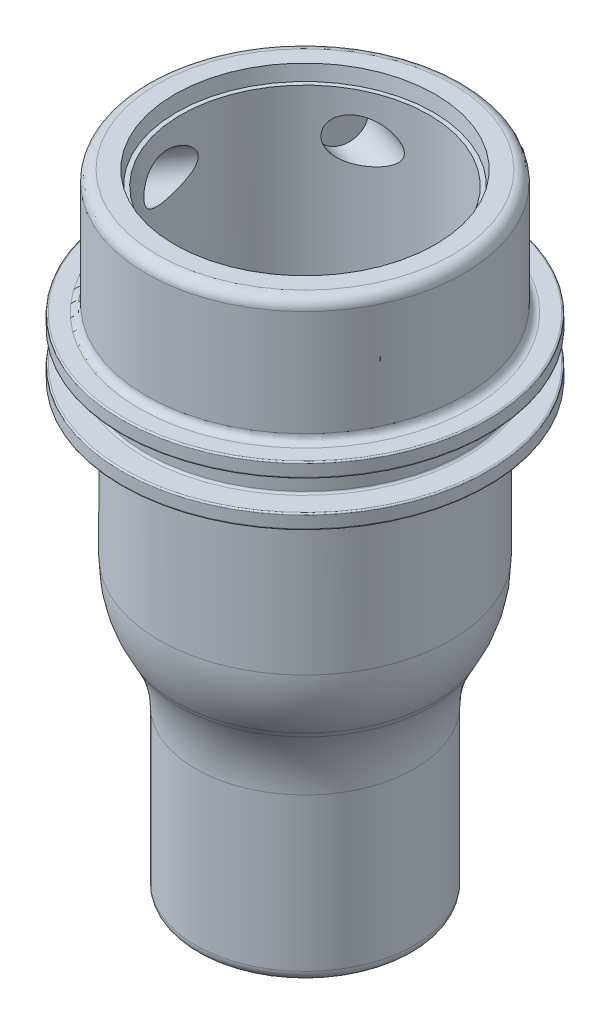
SolidWorks part; units mm, degrees
ref_plane "Front Plane" through (0, 0, 0) normal (0, 0, 1) x (1, 0, 0)
ref_plane "Top Plane" through (0, 0, 0) normal (0, 1, 0) x (1, 0, 0)
ref_plane "Right Plane" through (0, 0, 0) normal (1, 0, 0) x (0, 0, -1)
sketch "Sketch2" plane through (0, 0, 0) normal (0, 0, 1) x (1, 0, 0)
  line L0 (7.62, 0) -> (7.62, 17.145)
  line L1 (7.62, 17.145) -> (10.795, 22.6443)
  line L2 (10.795, 22.6443) -> (10.795, 53.4162)
  line L3 (0, 0) -> (0, 54.6862) construction
  line L4 (7.62, 0) -> (9.525, 0)
  line L5 (9.525, 0) -> (9.525, 17.145)
  line L6 (9.525, 17.145) -> (12.7, 22.6443)
  line L7 (12.7, 22.6443) -> (12.7, 38.735)
  line L8 (12.7, 38.735) -> (15.9385, 38.735)
  line L9 (15.9385, 38.735) -> (15.9385, 40.005)
  line L10 (15.9385, 40.005) -> (13.8176, 40.005)
  line L11 (13.8176, 40.005) -> (13.8176, 42.6212)
  line L12 (13.8176, 42.6212) -> (15.9385, 42.6212)
  line L13 (15.9385, 42.6212) -> (15.9385, 43.8912)
  line L14 (15.9385, 43.8912) -> (13.8176, 43.8912)
  line L15 (13.8176, 43.8912) -> (13.8176, 54.6862)
  line L16 (13.8176, 54.6862) -> (11.3432, 54.6862)
  line L17 (10.795, 53.4162) -> (11.176, 53.4162)
  line L19 (11.3432, 54.6862) -> (11.176, 53.4162)
  dimension "D2" = 0.381
  dimension "D3" = 19.05
  dimension "D4" = 1.905
  dimension "D5" = 1.905
  dimension "D6" = 30
  dimension "D7" = 17.145
  dimension "D8" = 38.735
  dimension "D9" = 31.877
  dimension "D10" = 27.6352
  dimension "D11" = 2.6162
  dimension "D12" = 1.27
  dimension "D13" = 9.525
  dimension "D14" = 25.4
  dimension "D15" = 1.27
  dimension "D16" = 7.5
  dimension "D17" = 22.352
  dimension "D18" = 22.6864
revolve "Revolve1" add sketch "Sketch2" angle 360 about L3
ref_axis "Centerline" through (0, 53.4162, 0) along (0, -1, 0)
fillet "O-Ring Gland R1" radius 0.1778 2 edges at (0, 40.005, -13.8176) (0, 42.6212, -13.8176)
fillet "O-Ring Gland R2" radius 0.127 4 edges at (0, 38.735, -15.9385) (0, 43.8912, -15.9385) (0, 40.005, -15.9385) (0, 42.6212, -15.9385)
fillet "O-Ring Gland Rounds" radius 0.635 2 edges at (0, 38.735, -12.7) (0, 43.8912, -13.8176)
fillet "Top/Bottom Rounds" radius 0.9525 3 edges at (0, 0, -9.525) (0, 0, -7.62) (0, 54.6862, -13.8176)
fillet "Flow Rounds" radius 10.795 4 edges at (0, 17.145, -9.525) (0, 22.6443, -12.7) (0, 17.145, -7.62) (0, 22.6443, -10.795)
sketch "Sketch3" plane through (0, 0, 0) normal (0, 0, 1) x (1, 0, 0)
  line L0 (11.176, 53.4162) -> (-11.176, 53.4162) construction
  line L1 (0, 53.4162) -> (0, 22.6443) construction
  circle A0 centre (7.62, 49.6062) radius 1.8669
  dimension "D1" = 3.7338
  dimension "D2" = 3.81
  dimension "D3" = 7.62
extrude "Cut-Extrude1" cut sketch "Sketch3" against normal blind 10.033 contours A0
pattern_circular "CirPattern1" count 5 over 360 about axis through (0, 0, 0) along (0, -1, 0) of "Cut-Extrude1"
